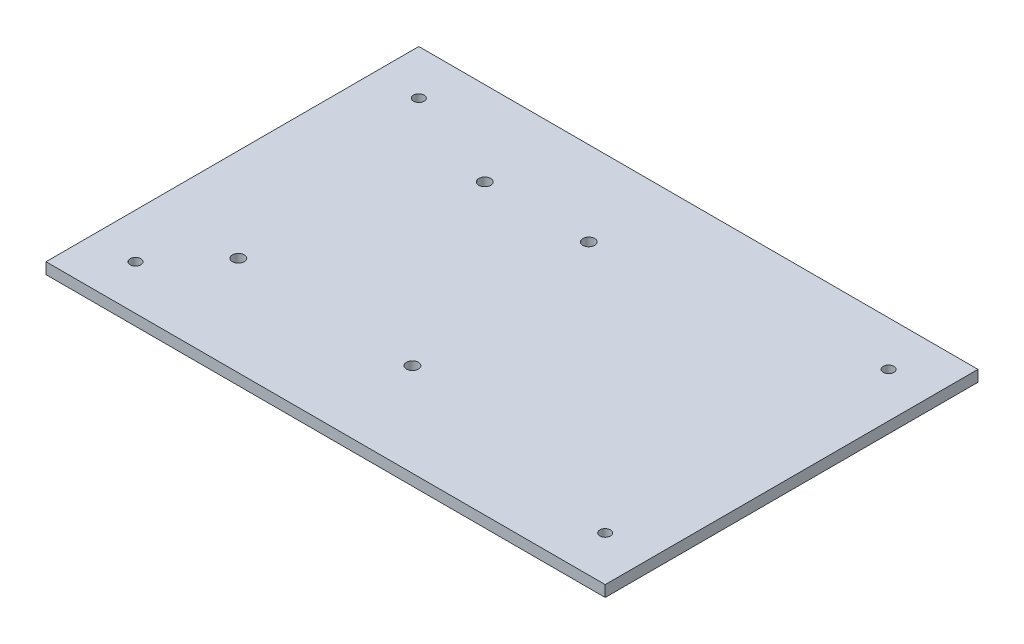
SolidWorks part; units mm, degrees
ref_plane "Front Plane" through (0, 0, 0) normal (0, 0, 1) x (1, 0, 0)
ref_plane "Top Plane" through (0, 0, 0) normal (0, 1, 0) x (1, 0, 0)
ref_plane "Right Plane" through (0, 0, 0) normal (1, 0, 0) x (0, 0, -1)
sketch "Sketch1" plane through (0, 0, 0) normal (0, 1, 0) x (1, 0, 0)
  line L1 (75, -50) -> (-75, -50)
  line L2 (75, -50) -> (75, 50)
  line L3 (75, 50) -> (-75, 50)
  line L4 (-75, -50) -> (-75, 50)
  line L5 (75, -50) -> (-75, 50) construction
  line L6 (75, 50) -> (-75, -50) construction
  point P0 (0, 0)
  dimension "D1" = 150
  dimension "D2" = 100
extrude "Boss-Extrude1" add sketch "Sketch1" along normal blind 3
sketch "Sketch2" plane through (0, 3, 0) normal (0, 1, 0) x (1, 0, 0)
  line L0 (0, 0) -> (-122.3191, 0) construction
  line L1 (-122.3191, 0) -> (115.1579, 0) construction
  line L2 (0, 73.5477) -> (0, -98.9538) construction
  line L3 (75, 50) -> (-75, 50) construction
  line L4 (-75, 50) -> (-75, -50) construction
  circle A0 centre (-63, 38) radius 1.425
  dimension "D1" = 2.85
  dimension "D2" = 12
  dimension "D3" = 12
extrude "Cut-Extrude1" cut sketch "Sketch2" against normal blind 10
pattern_linear "LPattern1" count 1 spacing 126 along (1, 0, 0) count 2 spacing 76 along (0, 0, 1) of "Cut-Extrude1"
sketch "Sketch3" [suppressed] plane through (0, 3, 0) normal (0, 1, 0) x (1, 0, 0)
  line L0 (47, 37) -> (-47, 37) construction
  line L1 (-47, 37) -> (-47, -37) construction
  circle A0 centre (-38, 28) radius 1.425
  dimension "D1" = 2.85
  dimension "D2" = 9
  dimension "D3" = 9
extrude "Cut-Extrude2" [suppressed] cut sketch "Sketch3" against normal blind 10
pattern_linear "LPattern2" [suppressed] count 2 spacing 76 count 2 spacing 56 of bodies 104
sketch "Sketch4" [suppressed] plane through (0, 3, 0) normal (0, 1, 0) x (1, 0, 0)
  line L0 (75, 37) -> (-75, 37) construction
  line L1 (-75, 37) -> (-75, -37) construction
  circle A0 centre (-63, 28) radius 1.425
  dimension "D1" = 2.85
  dimension "D2" = 9
  dimension "D3" = 12
extrude "Cut-Extrude3" [suppressed] cut sketch "Sketch4" against normal blind 10
pattern_linear "LPattern3" [suppressed] count 2 spacing 126 count 2 spacing 56 of bodies 106
sketch "Sketch5" plane through (0, 3, 0) normal (0, 1, 0) x (1, 0, 0)
  line L0 (-75, 50) -> (-75, -50) construction
  line L1 (-75, -50) -> (75, -50) construction
  line L3 (-1.7, -25) -> (-81.1724, -25) construction
  line L4 (-6.8, 27.4) -> (-34.7, 27.4) construction
  circle A0 centre (-34.7, 27.4) radius 1.6
  circle A1 centre (-6.8, 27.4) radius 1.6
  circle A2 centre (-1.7, -25) radius 1.6
  circle A4 centre (-50, -23.4) radius 1.6
  dimension "D1" = 3.2
  dimension "D2" = 27.9
  dimension "D3" = 5.1
  dimension "D4" = 50.8
  dimension "D5" = 48.3
  dimension "D6" = 25
  dimension "D7" = 25
extrude "Cut-Extrude4" cut sketch "Sketch5" against normal blind 10
sketch "Sketch6" plane through (0, 0, 0) normal (0, -1, 0) x (1, 0, 0)
  line L0 (-63, 38) -> (100.028, 38) construction
  line L1 (75, 50) -> (75, -50) construction
  line L2 (63, 38) -> (63, -100.5192) construction
  line L3 (-63, -38) -> (102.189, -38) construction
  circle A0 centre (63, 38) radius 1.425
  circle A3 centre (63, -38) radius 1.425
  dimension "D2" = 2.85
  dimension "D1" = 12
extrude "Cut-Extrude5" cut sketch "Sketch6" against normal blind 10
sketch "Sketch7" [suppressed] plane through (0, 3, 0) normal (0, 1, 0) x (1, 0, 0)
  line L0 (-47, 37) -> (-47, -37) construction
  line L1 (47, 37) -> (-47, 37)
  line L2 (47, 37) -> (47, 35.24)
  line L3 (47, 35.24) -> (-47, 35.24)
  line L4 (-47, 37) -> (-47, 35.24)
  dimension "D1" = 1.76
extrude "Cut-Extrude6" [suppressed] cut sketch "Sketch7" against normal blind 10
sketch "Sketch8" [suppressed] plane through (-47, 0, 0) normal (-1, 0, 0) x (0, 0, 1)
  line L0 (-35.24, 0) -> (37, 0) construction
  line L1 (-35.24, 3) -> (-20.24, 3)
  line L2 (-35.24, 3) -> (-35.24, 0)
  line L3 (-35.24, 0) -> (-20.24, 0)
  line L4 (-20.24, 3) -> (-20.24, 0)
  dimension "D1" = 15
extrude "Boss-Extrude2" [suppressed] add sketch "Sketch8" along normal blind 3
mirror "Mirror1" [suppressed] about plane through (0, 0, 0) normal (1, 0, 0)
sketch "Sketch9" [suppressed] plane through (0, 3, 0) normal (0, 1, 0) x (1, 0, 0)
  line L0 (-75, -50) -> (75, -50) construction
  line L1 (75, 50) -> (70.31, 50)
  line L2 (75, 50) -> (75, -50)
  line L3 (75, -50) -> (70.31, -50)
  line L4 (70.31, 50) -> (70.31, -50)
  dimension "D1" = 4.69
extrude "Cut-Extrude7" [suppressed] cut sketch "Sketch9" against normal blind 10
sketch "Sketch10" [suppressed] plane through (0, 3, 0) normal (0, 1, 0) x (1, 0, 0)
  line L0 (-101.381, 0) -> (123.8175, 0) construction
  line L1 (0, 45.5263) -> (0, -61.4392) construction
  circle A0 centre (-45, 0) radius 3.625
  circle A1 centre (-15, 0) radius 3.625
  circle A2 centre (15, 0) radius 3.625
  circle A3 centre (45, 0) radius 3.625
  dimension "D1" = 7.25
  dimension "D2" = 15
  dimension "D3" = 30
extrude "Cut-Extrude8" [suppressed] cut sketch "Sketch10" against normal blind 10
sketch "Sketch11" [suppressed] plane through (0, 0, 0) normal (0, -1, 0) x (1, 0, 0)
  line L0 (-126.9736, 0) -> (96.4357, 0) construction
  line L1 (-34.8, 0) -> (-34.8, 5.5) construction
  line L2 (-35.6, 0) -> (-35.6, 5.5)
  line L3 (-34, 0) -> (-34, 5.5)
  line L4 (0, 50.3887) -> (0, -44.5353) construction
  arc A0 (-38.9163, 4.0147) -> (-30.4291, 3.7359) centre (-34.8, 0) ccw construction
  arc A1 (-39.4533, 4.5384) -> (-29.8589, 4.2232) centre (-34.8, 0) ccw
  arc A2 (-38.3794, 3.4911) -> (-30.9992, 3.2487) centre (-34.8, 0) ccw
  arc A3 (-38.3794, 3.4911) -> (-39.4533, 4.5384) centre (-38.9163, 4.0147) ccw
  arc A4 (-29.8589, 4.2232) -> (-30.9992, 3.2487) centre (-30.4291, 3.7359) ccw
  arc A5 (-35.6, 0) -> (-34, 0) centre (-34.8, 0) ccw
  arc A6 (-34, 5.5) -> (-35.6, 5.5) centre (-34.8, 5.5) ccw
  point P6 (-34.9888, -5.7469)
  point P13 (-34.8, 2.75)
  point P20 (-30.9163, 4.3061)
  dimension "D1" = 6.5
  dimension "D3" = 0.8
  dimension "D5" = 5
  dimension "D7" = 5.7469
  dimension "D2" = 5.5
  dimension "D4" = 8
  dimension "D6" = 34
extrude "Cut-Extrude9" [suppressed] cut sketch "Sketch11" against normal blind 10
sketch "Sketch12" [suppressed] plane through (0, 0, 0) normal (0, -1, 0) x (1, 0, 0)
  line L0 (-84.8642, 0) -> (86.8315, 0) construction
  circle A0 centre (-15, 0) radius 4
  dimension "D1" = 8
  dimension "D2" = 15
extrude "Cut-Extrude10" [suppressed] cut sketch "Sketch12" against normal blind 10
pattern_linear "LPattern4" [suppressed] count 2 spacing 20 of bodies 116
sketch "Sketch13" [suppressed] plane through (0, 3, 0) normal (0, 1, 0) x (1, 0, 0)
  line L0 (97.8196, 0) -> (-126.0628, 0) construction
  circle A0 centre (18.87, 0) radius 1.25
  circle A1 centre (-8.38, 0) radius 1.25
  dimension "D1" = 2.5
  dimension "D2" = 27.25
extrude "Cut-Extrude11" [suppressed] cut sketch "Sketch13" against normal blind 10
sketch "Sketch15" [suppressed] plane through (0, 3, 0) normal (0, 1, 0) x (1, 0, 0)
  line L0 (0, -17.7932) -> (0, 22.7245) construction
  line L1 (-22.619, 0) -> (26.3, 0) construction
  line L3 (17.07, -7) -> (-6.58, -7)
  line L4 (17.07, -7) -> (17.07, 7)
  line L5 (17.07, 7) -> (-6.58, 7)
  line L6 (-6.58, -7) -> (-6.58, 7)
  circle A0 centre (18.87, 0) radius 1.25 construction
  circle A1 centre (-8.38, 0) radius 1.25 construction
  dimension "D1" = 1.8
  dimension "D2" = 1.8
  dimension "D3" = 14
extrude "Cut-Extrude12" [suppressed] cut sketch "Sketch15" against normal blind 10
